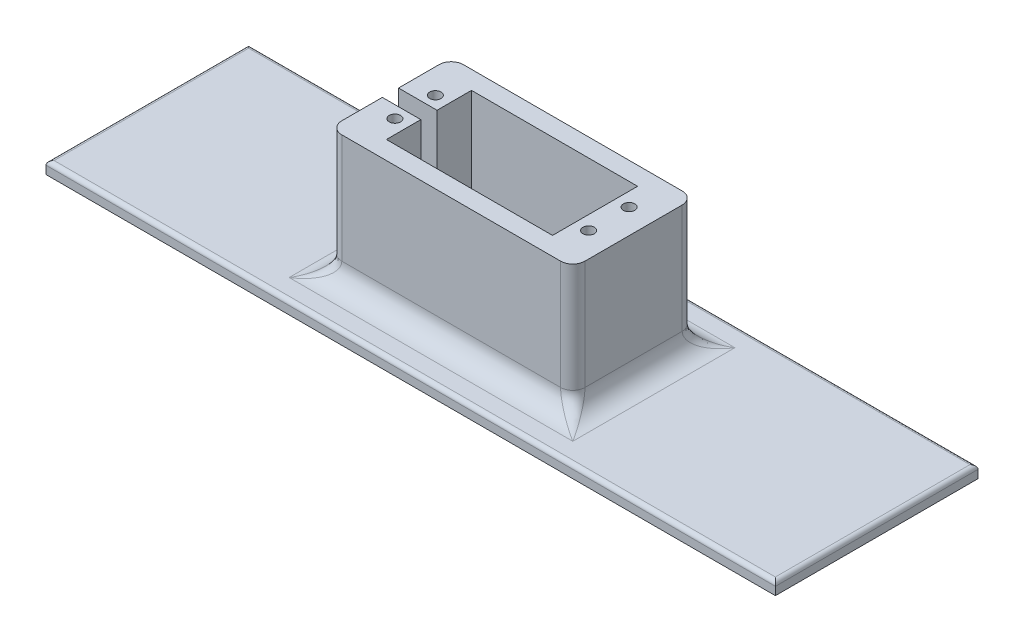
SolidWorks part; units mm, degrees
ref_plane "Front Plane" through (0, 0, 0) normal (0, 0, 1) x (1, 0, 0)
ref_plane "Top Plane" through (0, 0, 0) normal (0, 1, 0) x (1, 0, 0)
ref_plane "Right Plane" through (0, 0, 0) normal (1, 0, 0) x (0, 0, -1)
sketch "Sketch1" plane through (0, 0, 0) normal (0, 1, 0) x (1, 0, 0)
  line L8 (0, 15) -> (60, 15) construction
  line L9 (0, 0) -> (60, 0)
  line L10 (0, 0) -> (0, 30)
  line L11 (0, 30) -> (60, 30)
  line L12 (60, 0) -> (60, 30)
  line L13 (30, 30) -> (30, 0) construction
  line L15 (9.5, 4.5) -> (50.5, 4.5)
  line L16 (9.5, 4.5) -> (9.5, 25.5)
  line L17 (9.5, 25.5) -> (50.5, 25.5)
  line L18 (50.5, 4.5) -> (50.5, 25.5)
  line L19 (9.5, 4.5) -> (50.5, 25.5) construction
  line L20 (9.5, 25.5) -> (50.5, 4.5) construction
  line L21 (-60, -10) -> (120, -10)
  line L22 (-60, -10) -> (-60, 40)
  line L23 (-60, 40) -> (120, 40)
  line L24 (120, -10) -> (120, 40)
  line L25 (-60, -10) -> (120, 40) construction
  line L26 (-60, 40) -> (120, -10) construction
  circle A0 centre (6.1, 20) radius 1.4
  circle A1 centre (53.9, 20) radius 1.4
  circle A2 centre (53.9, 10) radius 1.4
  circle A3 centre (6.1, 10) radius 1.4
  point P11 (30, 15)
  point P18 (30, 15)
  point P23 (30, 15)
  point P29 (0, 0)
  point P33 (0, 0)
  point P34 (0, 0)
  point P35 (0, 0)
  point P36 (0, 0)
  point P37 (0, 0)
  point P38 (0, 0)
  point P39 (0, 0)
  dimension "D3" = 2.8
  dimension "D1" = 60
  dimension "D2" = 30
  dimension "D4" = 10
  dimension "D5" = 47.8
  dimension "D6" = 41
  dimension "D7" = 21
  dimension "D8" = 50
  dimension "D9" = 180
extrude "Boss-Extrude2" add sketch "Sketch1" along normal blind 3 contours L21 L24 L23 L22 L12 L9 L10 L11 region at (-58.1318, 0, -15)
extrude "Boss-Extrude3" add sketch "Sketch1<4>" along normal blind 35 contours L9 L12 L11 L10 A1 A0 L18 L15 L16 L17 A2 A3 region at (0.6708, 0, -15)
sketch "Sketch1<4>" plane through (0, 0, 0) normal (0, 1, 0) x (1, 0, 0) same geometry as "Sketch1"
extrude "Boss-Extrude4" add sketch "Sketch1<5>" along normal blind 25 contours A3 | A0 | A2 | A1
sketch "Sketch1<5>" plane through (0, 0, 0) normal (0, 1, 0) x (1, 0, 0) same geometry as "Sketch1"
sketch "Sketch2" plane through (0, 0, 0) normal (-1, 0, 0) x (0, 0, 1)
  line L0 (-17, 35) -> (-17, 12)
  line L1 (0, 35) -> (-30, 35) construction
  line L2 (-17, 12) -> (-18, 11)
  line L3 (-18, 11) -> (-18, 3)
  line L4 (0, 3) -> (-30, 3) construction
  line L5 (-15, 35) -> (-15, 3) construction
  line L6 (-12, 11) -> (-12, 3)
  line L7 (-13, 12) -> (-12, 11)
  line L8 (-13, 35) -> (-13, 12)
  line L9 (-17, 35) -> (-13, 35)
  line L10 (-18, 3) -> (-12, 3)
  dimension "D1" = 4
  dimension "D2" = 6
  dimension "D3" = 135
  dimension "D4" = 8
extrude "Cut-Extrude1" cut sketch "Sketch2" against normal up to next
fillet "Fillet2" radius 5 5 edges at (60, 3, -15) (30, 3, -30) (0, 3, -24) (0, 3, -6) (30, 3, 0)
fillet "Fillet3" radius 3 8 edges at (61.4645, 4.4645, 1.4645) (61.4645, 4.4645, -31.4645) (-1.4645, 4.4645, 1.4645) (-1.4645, 4.4645, -31.4645) (60, 21.5, 0) (60, 21.5, -30) (0, 21.5, 0) (0, 21.5, -30)
fillet "Fillet4" radius 1 4 edges at (-60, 3, -15) (30, 3, -40) (120, 3, -15) (30, 3, 10)
fillet "Fillet5" radius 1 4 edges at (4.75, 11, -12) (4.75, 12, -13) (4.75, 11, -18) (4.75, 12, -17)
fillet "Fillet6" radius 1 2 edges at (2.25, 3, -12) (2.25, 3, -18)
